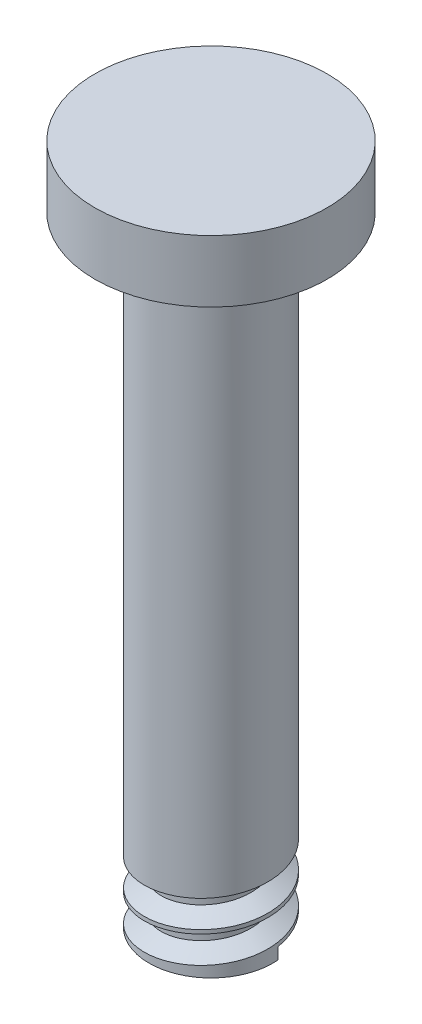
SolidWorks part; units mm, degrees
ref_plane "Front Plane" through (0, 0, 0) normal (0, 0, 1) x (1, 0, 0)
ref_plane "Top Plane" through (0, 0, 0) normal (0, 1, 0) x (1, 0, 0)
ref_plane "Right Plane" through (0, 0, 0) normal (1, 0, 0) x (0, 0, -1)
sketch "Sketch2" plane through (0, 0, 0) normal (0, 1, 0) x (1, 0, 0)
  circle A0 centre (0, 0) radius 7.5
extrude "Boss-Extrude1" add sketch "Sketch2" along normal blind 4
sketch "Sketch3" plane through (0, 0, 0) normal (0, -1, 0) x (-1, 0, 0)
  circle A0 centre (0, 0) radius 4
extrude "Boss-Extrude2" add sketch "Sketch3" along normal blind 40
thread "Thread1" pitch 2 method cut profile "Thread Profile2" start angle 5, offset 1, length 5, pitch 2, diameter 8
ref_plane "Plane2" through (3.9848, -41, -0.3486) normal (0.0872, 0, 0.9962) x (0.9962, 0, -0.0872)
sketch "Thread Profile2" plane through (3.9848, -41, -0.3486) normal (0.0872, 0, 0.9962) x (0.9962, 0, -0.0872)
  line L0 (0, 0) -> (0, 2) construction
  line L11 (0, 0) -> (0, 1.75)
  line L12 (0, 1.75) -> (-1.0825, 1.125)
  line L13 (-1.0825, 1.125) -> (-1.0825, 0.625)
  line L15 (-1.0825, 0.625) -> (0, 0)
  line L17 (-1.0825, 0.875) -> (0, 0.875) construction
  point P2 (0, 0)
  dimension "Pitch" = 2
  dimension "Profile_Angle" = 60
  dimension "Profile_Land" = 0.5
  dimension "Profile_Height" = 1.0825
